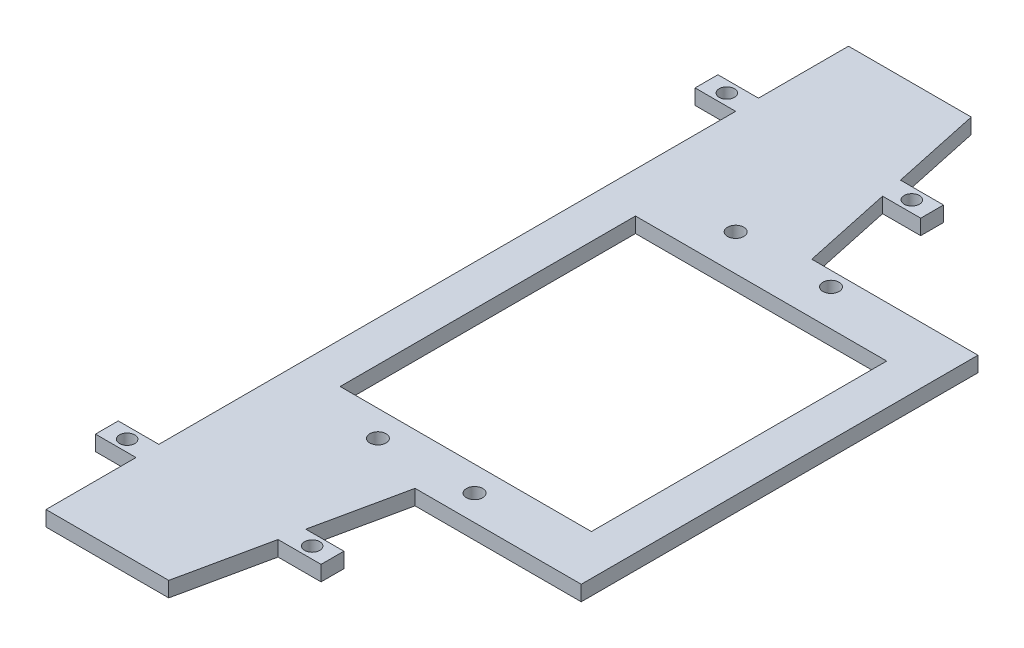
SolidWorks part; units mm, degrees
ref_plane "Front Plane" through (0, 0, 0) normal (0, 0, 1) x (1, 0, 0)
ref_plane "Top Plane" through (0, 0, 0) normal (0, 1, 0) x (1, 0, 0)
ref_plane "Right Plane" through (0, 0, 0) normal (1, 0, 0) x (0, 0, -1)
sketch "Sketch1" plane through (0, 0, 0) normal (0, 1, 0) x (1, 0, 0)
  line L0 (0, 39.1145) -> (0, -39.1145)
  line L1 (0, -39.1145) -> (65.532, -39.1145)
  line L2 (65.532, -39.1145) -> (65.532, 39.1145)
  line L3 (65.532, 39.1145) -> (0, 39.1145)
  line L4 (0, 39.1145) -> (0, 79.1145)
  line L5 (0, 79.1145) -> (24.2, 79.1145)
  line L6 (24.2, 79.1145) -> (32.766, 39.1145)
  line L7 (0, 39.1145) -> (32.766, 39.1145)
  line L8 (0, -39.1145) -> (0, -79.1145)
  line L9 (-8, 61.3645) -> (8, 61.3645)
  line L10 (-8, 61.3645) -> (-8, 56.8645)
  line L11 (-8, 56.8645) -> (8, 56.8645)
  line L12 (8, 61.3645) -> (8, 56.8645)
  line L13 (-40.4426, 0) -> (40.4426, 0) construction
  line L14 (8, 29.1145) -> (57.532, 29.1145)
  line L15 (20.483, 61.3645) -> (36.483, 61.3645)
  line L16 (20.483, 61.3645) -> (20.483, 56.8645)
  line L17 (20.483, 56.8645) -> (36.483, 56.8645)
  line L18 (36.483, 61.3645) -> (36.483, 56.8645)
  line L19 (8, 29.1145) -> (8, -29.1145)
  line L20 (8, -29.1145) -> (57.532, -29.1145)
  line L21 (0, -87.026) -> (0, 87.026) construction
  line L22 (0, -79.1145) -> (24.2, -79.1145)
  line L23 (24.2, -79.1145) -> (32.766, -39.1145)
  line L24 (32.766, -39.1145) -> (0, -39.1145)
  line L25 (57.532, 29.1145) -> (57.532, -29.1145)
  line L26 (20.483, -56.8645) -> (36.483, -56.8645)
  line L27 (20.483, -56.8645) -> (20.483, -61.3645)
  line L28 (20.483, -61.3645) -> (36.483, -61.3645)
  line L29 (36.483, -56.8645) -> (36.483, -61.3645)
  line L30 (8, 29.1145) -> (57.532, -29.1145) construction
  line L31 (8, -29.1145) -> (57.532, 29.1145) construction
  line L32 (-8, -56.8645) -> (8, -56.8645)
  line L33 (-8, -56.8645) -> (-8, -61.3645)
  line L34 (-8, -61.3645) -> (8, -61.3645)
  line L35 (8, -56.8645) -> (8, -61.3645)
  circle A0 centre (20.574, 36.2868) radius 1.6
  circle A1 centre (39.37, 36.2868) radius 1.5999
  circle A2 centre (20.574, -34.2415) radius 1.6
  circle A3 centre (39.4509, -34.0685) radius 1.5999
  circle A4 centre (-4, 59.1145) radius 1.5
  circle A5 centre (32.483, 59.1145) radius 1.5
  circle A6 centre (-4, -59.1145) radius 1.5
  circle A8 centre (32.483, -59.1145) radius 1.5
  point P8 (0, 59.1145)
  point P21 (28.483, 59.1145)
  point P30 (28.483, -59.1145)
  point P40 (0, -59.1145)
  point P47 (32.766, 0)
  point P56 (0, 0)
  dimension "D12" = 3
  dimension "D14" = 3
  dimension "D23" = 3
  dimension "D24" = 4
  dimension "D26" = 3
  dimension "D27" = 10
  dimension "D1" = 65.532
  dimension "D2" = 78.229
  dimension "D3" = 40
  dimension "D4" = 24.2
  dimension "D5" = 10
  dimension "D6" = 40
  dimension "D7" = 16
  dimension "D8" = 16
  dimension "D9" = 4.5
  dimension "D10" = 4.5
  dimension "D11" = 8
  dimension "D13" = 4
  dimension "D15" = 4
  dimension "D16" = 44.483
  dimension "D17" = 40
  dimension "D18" = 24.2
  dimension "D19" = 16
  dimension "D20" = 16
  dimension "D21" = 4.5
  dimension "D22" = 4.5
  dimension "D25" = 4
  dimension "D28" = 8
  dimension "D29" = 8
  dimension "D30" = 2.25
  dimension "D31" = 2.25
  dimension "D32" = 2.25
  dimension "D33" = 2.25
extrude "Boss-Extrude1" add sketch "Sketch1" along normal blind 3 contours L10 L11 L4 L9 A4 | L12 L9 L4 L11 | L17 L16 L15 L6 L5 L4 L9 L12 L11 L3 | L16 L17 L6 L15 | L18 L15 L6 L17 A5 | L2 L3 L0 L1 A3 A2 A1 A0 L14 L25 L20 L19 | L32 L35 L34 L8 L22 L23 L28 L27 L26 L1 | L27 L28 L23 L26 | L29 L26 L23 L28 A8 | L35 L32 L8 L34 | L33 L34 L8 L32 A6 region at (16.383, 0, -38.094) region at (14.3559, 0, -58.0459) region at (14.3559, 0, 58.0459) region at (-4, 0, -56.9563) region at (4, 0, -59.1145) region at (4, 0, 59.1145) region at (-0.0918, 0, 59.1145) region at (24.4878, 0, -59.0693) region at (28.5769, 0, -59.1346) region at (32.7239, 0, 56.9605) region at (24.4878, 0, 59.0693)
